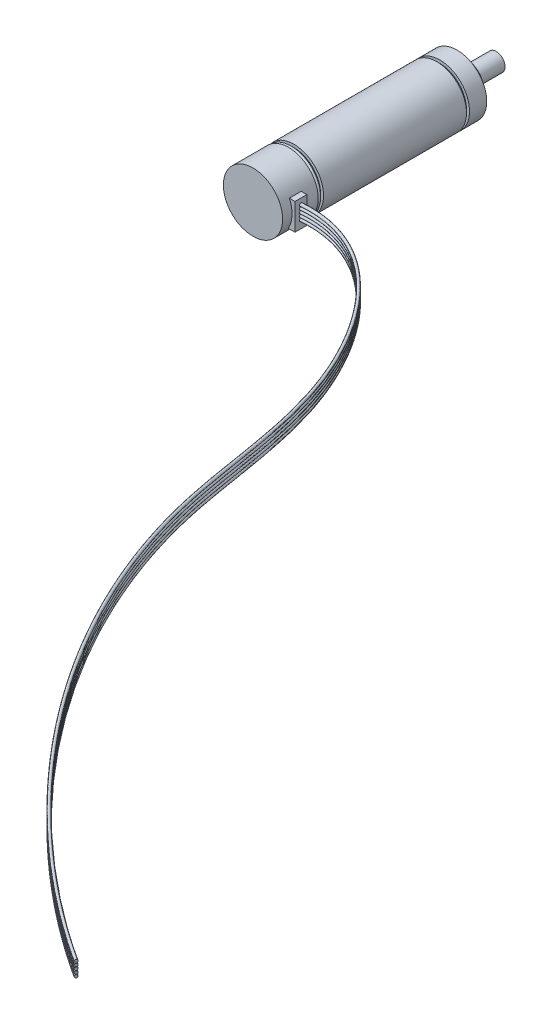
SolidWorks part; units mm, degrees
ref_plane "前基準面" through (0, 0, 0) normal (0, 0, 1) x (1, 0, 0)
ref_plane "上基準面" through (0, 0, 0) normal (0, 1, 0) x (1, 0, 0)
ref_plane "右基準面" through (0, 0, 0) normal (1, 0, 0) x (0, 0, -1)
sketch "草圖1" plane through (0, 0, 0) normal (0, 0, 1) x (1, 0, 0)
  circle A0 centre (0, 0) radius 5
  dimension "D1" = 10
extrude "填料-伸長1" add sketch "草圖1" along normal blind 0.9
chamfer "導角2" distance 0.5 angle 45 1 edges at (5, 0, 0)
sketch "草圖2" plane through (0, 0, 0) normal (0, 0, -1) x (-1, 0, 0)
  circle A0 centre (0, 0) radius 5
  dimension "D1" = 10
extrude "填料-伸長2" add sketch "草圖2" along normal blind 24.6
chamfer "導角4" distance 0.5 angle 45 1 edges at (-5, 0, -24.6)
sketch "草圖3" plane through (0, 0, -24.6) normal (0, 0, -1) x (-1, 0, 0)
  circle A0 centre (0, 0) radius 5
  dimension "D1" = 10
extrude "填料-伸長3" add sketch "草圖3" along normal blind 2.9
sketch "草圖4" plane through (0, 0, -27.5) normal (0, 0, -1) x (-1, 0, 0)
  circle A0 centre (0, 0) radius 3
  dimension "D1" = 6
extrude "填料-伸長4" add sketch "草圖4" along normal blind 1.5
sketch "草圖5" plane through (0, 0, -29) normal (0, 0, -1) x (-1, 0, 0)
  circle A0 centre (0, 0) radius 1.5
  dimension "D1" = 3
extrude "填料-伸長5" add sketch "草圖5" along normal blind 5.1
chamfer "導角6" distance 0.5 angle 45 1 edges at (5, 0, 0.9)
sketch "草圖12" plane through (0, 0, 0.9) normal (0, 0, 1) x (1, 0, 0)
  circle A0 centre (0, 0) radius 4.9965
extrude "填料-伸長6" add sketch "草圖12" along normal blind 6
sketch "草圖13" plane through (0, 0, 0) normal (1, 0, 0) x (0, 0, -1)
  line L1 (-5.3141, 2.0585) -> (-3.3141, 2.0585)
  line L2 (-5.3141, 2.0585) -> (-5.3141, -2.4415)
  line L3 (-5.3141, -2.4415) -> (-3.3141, -2.4415)
  line L4 (-3.3141, 2.0585) -> (-3.3141, -2.4415)
  line L5 (-5.3141, 2.0585) -> (-3.3141, -2.4415) construction
  line L6 (-5.3141, -2.4415) -> (-3.3141, 2.0585) construction
  point P0 (-4.3141, -0.1915)
  dimension "D1" = 4.5
  dimension "D2" = 2
extrude "填料-伸長7" add sketch "草圖13" along normal blind 5.5
sketch "草圖14" plane through (5.5, 0, 0) normal (1, 0, 0) x (0, 0, -1)
  circle A1 centre (-4.3141, 0) radius 0.25
  dimension "D1" = 0.5
sketch "草圖16" plane through (0, 0, 0) normal (0, 1, 0) x (1, 0, 0)
  line L1 (5.5, -3.3141) -> (5.5, -5.3141) construction
  spline S0 degree 3 poles (5.5, -4.3141) (18.0142, -3.2384) (36.0576, -25.8731) (38.6682, -79.4251) (71.0426, -116.9628) (97.0107, -133.7245) knots 0 0 0 0 0.224562 0.406424 1 1 1 1
sweep "掃出2" add profiles "草圖14" path "草圖16"
pattern_linear "直線複製排列4" count 4 spacing 0.55 along (0, -1, 0) count 4 spacing 0.55 along (0, 1, 0) skipping (0, 3), (3, 0) of "掃出2"
